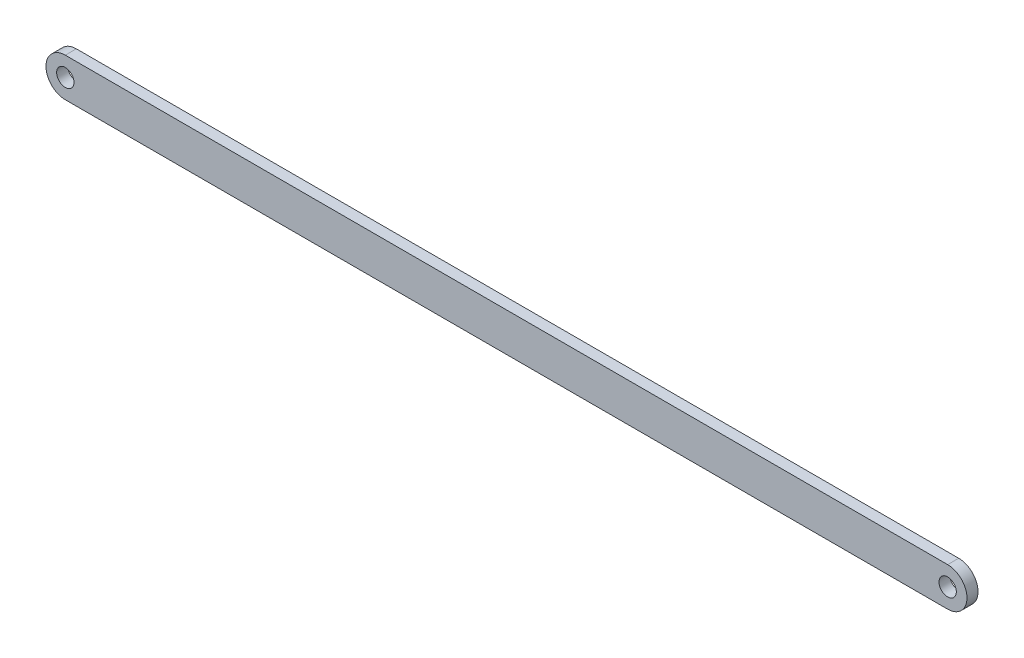
SolidWorks part; units mm, degrees
ref_plane "Front Plane" through (0, 0, 0) normal (0, 0, 1) x (1, 0, 0)
ref_plane "Top Plane" through (0, 0, 0) normal (0, 1, 0) x (1, 0, 0)
ref_plane "Right Plane" through (0, 0, 0) normal (1, 0, 0) x (0, 0, -1)
sketch "Sketch1" plane through (0, 0, 0) normal (0, 0, 1) x (1, 0, 0)
  line L1 (-101.6, 4.445) -> (101.6, 4.445)
  line L2 (-101.6, 4.445) -> (-101.6, -4.445)
  line L3 (-101.6, -4.445) -> (101.6, -4.445)
  line L4 (101.6, 4.445) -> (101.6, -4.445)
  line L5 (-101.6, 4.445) -> (101.6, -4.445) construction
  line L6 (-101.6, -4.445) -> (101.6, 4.445) construction
  circle A0 centre (-101.6, 0) radius 4.445
  circle A1 centre (101.6, 0) radius 4.445
  circle A2 centre (-101.6, 0) radius 1.9939
  circle A3 centre (101.6, 0) radius 1.9939
  point P0 (0, 0)
  point P11 (-101.6, 0)
  point P13 (101.6, 0)
  dimension "D3" = 8.89
  dimension "D4" = 8.89
  dimension "D5" = 3.9878
  dimension "D6" = 3.9878
  dimension "D1" = 8.89
  dimension "D2" = 203.2
extrude "Boss-Extrude1" add sketch "Sketch1" along normal blind 2.54 contours A1 L1 A0 L3 | A2 L2 A0 | A2 L2 A0 | A3 L4 A1 | A3 L4 A1 region at (-99.4514, 0, 0) region at (0, 0, 0) region at (-103.7486, 0, 0) region at (103.7486, 0, 0) region at (99.4514, 0, 0)
